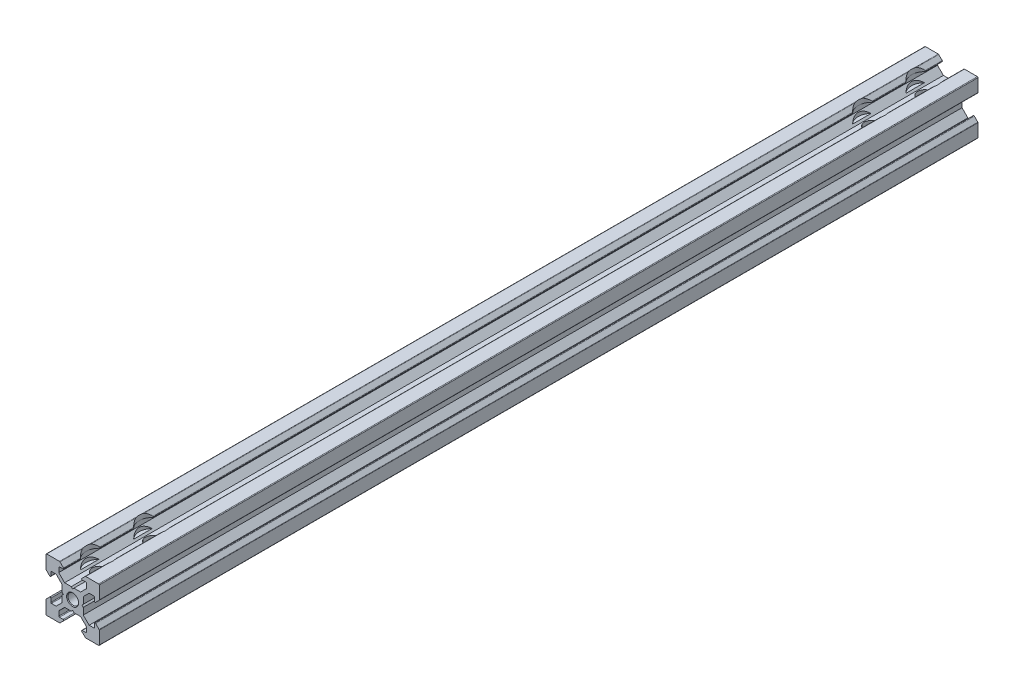
SolidWorks part; units mm, degrees
material "3.0205 (EN-AW 1200)"
ref_plane "Alzado" through (0, 0, 0) normal (0, 0, 1) x (1, 0, 0)
ref_plane "Planta" through (0, 0, 0) normal (0, 1, 0) x (1, 0, 0)
ref_plane "Vista lateral" through (0, 0, 0) normal (1, 0, 0) x (0, 0, -1)
sketch "Croquis1" plane through (0, 0, 0) normal (0, 0, 1) x (1, 0, 0)
  line L0 (-3.9878, 0.4994) -> (-3.4878, -0.0006)
  line L43 (0.0115, 3.5003) -> (-0.4882, 4)
  line L44 (-0.4882, 4) -> (-2.9967, 4)
  line L45 (-2.9967, 4) -> (-5.1969, 6.2003)
  line L46 (-5.1969, 6.2003) -> (-5.1969, 7.9432)
  line L47 (-4.9469, 8.1932) -> (-3.6023, 8.1932)
  line L53 (-7.9369, 5.2103) -> (-6.1869, 5.2103)
  line L54 (-6.1869, 5.2103) -> (-3.9878, 3.0113)
  line L55 (-3.9878, 3.0113) -> (-3.9878, 0.4994)
  line L58 (-8.1869, 4.9603) -> (-8.1869, 3.602)
  line L60 (-9.9869, 9.7494) -> (-9.9869, 4.902)
  line L61 (-9.7369, 9.9994) -> (-4.9084, 9.9994)
  line L62 (-8.6137, 3.4252) -> (-9.9137, 4.7252)
  line L64 (6.2124, 5.2094) -> (7.9554, 5.2094)
  line L65 (-3.4255, 8.62) -> (-4.7316, 9.9261)
  line L66 (4.0122, 3.0091) -> (6.2124, 5.2094)
  line L67 (4.0122, 0.5007) -> (4.0122, 3.0091)
  line L68 (3.5124, 0.001) -> (4.0122, 0.5007)
  line L71 (0.5115, 4.0003) -> (0.0115, 3.5003)
  line L72 (3.0234, 4.0003) -> (0.5115, 4.0003)
  line L73 (5.2225, 6.1994) -> (3.0234, 4.0003)
  line L74 (5.2225, 7.9494) -> (5.2225, 6.1994)
  line L75 (4.9725, 8.1994) -> (3.6141, 8.1994)
  line L76 (3.4374, 8.6261) -> (4.7374, 9.9261)
  line L77 (9.7615, 9.9994) -> (4.9141, 9.9994)
  line L78 (10.0115, 9.7494) -> (10.0115, 4.9208)
  line L79 (8.6322, 3.4379) -> (9.9383, 4.744)
  line L80 (8.2054, 4.9594) -> (8.2054, 3.6147)
  line L81 (5.2216, -6.2) -> (5.2216, -7.9429)
  line L82 (3.0213, -3.9997) -> (5.2216, -6.2)
  line L83 (0.5128, -3.9997) -> (3.0213, -3.9997)
  line L84 (0.0131, -3.5) -> (0.5128, -3.9997)
  line L87 (4.0124, -0.499) -> (3.5124, 0.001)
  line L88 (4.0124, -3.011) -> (4.0124, -0.499)
  line L89 (6.2115, -5.21) -> (4.0124, -3.011)
  line L90 (7.9615, -5.21) -> (6.2115, -5.21)
  line L91 (8.2115, -4.96) -> (8.2115, -3.6017)
  line L92 (8.6383, -3.4249) -> (9.9383, -4.7249)
  line L93 (10.0115, -9.749) -> (10.0115, -4.9017)
  line L94 (9.7615, -9.999) -> (4.933, -9.999)
  line L95 (3.4501, -8.6197) -> (4.7562, -9.9258)
  line L96 (4.9716, -8.1929) -> (3.6269, -8.1929)
  line L97 (-6.1878, -5.2091) -> (-7.9308, -5.2091)
  line L98 (-3.9876, -3.0088) -> (-6.1878, -5.2091)
  line L99 (-3.9876, -0.5004) -> (-3.9876, -3.0088)
  line L100 (-3.4878, -0.0006) -> (-3.9876, -0.5004)
  line L103 (-0.4869, -4) -> (0.0131, -3.5)
  line L104 (-2.9988, -4) -> (-0.4869, -4)
  line L105 (-5.1247, -6.1258) -> (-2.9988, -4)
  line L106 (-5.1979, -7.949) -> (-5.1979, -6.3026)
  line L107 (-4.9479, -8.199) -> (-3.5895, -8.199)
  line L108 (-3.4127, -8.6258) -> (-4.7127, -9.9258)
  line L109 (-9.7369, -9.999) -> (-4.8895, -9.999)
  line L110 (-9.9869, -9.749) -> (-9.9869, -4.9205)
  line L111 (-8.6076, -3.4376) -> (-9.9137, -4.7437)
  line L112 (-8.1808, -4.9591) -> (-8.1808, -3.6144)
  arc A0 (10.0115, -9.749) -> (9.7615, -9.999) centre (9.7615, -9.749) cw
  arc A1 (-9.7369, -9.999) -> (-9.9869, -9.749) centre (-9.7369, -9.749) cw
  arc A2 (10.0115, 9.7494) -> (9.7615, 9.9994) centre (9.7615, 9.7494) ccw
  arc A3 (-9.7369, 9.9994) -> (-9.9869, 9.7494) centre (-9.7369, 9.7494) ccw
  arc A4 (8.2115, -3.6017) -> (8.6383, -3.4249) centre (8.4615, -3.6017) cw
  arc A5 (7.9615, -5.21) -> (8.2115, -4.96) centre (7.9615, -4.96) ccw
  arc A6 (5.2216, -7.9429) -> (4.9716, -8.1929) centre (4.9716, -7.9429) cw
  arc A7 (3.4501, -8.6197) -> (3.6269, -8.1929) centre (3.6269, -8.4429) cw
  arc A8 (-3.5895, -8.199) -> (-3.4127, -8.6258) centre (-3.5895, -8.449) cw
  arc A9 (-5.1979, -7.949) -> (-4.9479, -8.199) centre (-4.9479, -7.949) ccw
  arc A10 (-5.1247, -6.1258) -> (-5.1979, -6.3026) centre (-4.9479, -6.3026) ccw
  arc A11 (-7.9308, -5.2091) -> (-8.1808, -4.9591) centre (-7.9308, -4.9591) cw
  arc A12 (-8.6076, -3.4376) -> (-8.1808, -3.6144) centre (-8.4308, -3.6144) cw
  arc A13 (8.6322, 3.4379) -> (8.2054, 3.6147) centre (8.4554, 3.6147) cw
  arc A14 (7.9554, 5.2094) -> (8.2054, 4.9594) centre (7.9554, 4.9594) cw
  arc A15 (5.2225, 7.9494) -> (4.9725, 8.1994) centre (4.9725, 7.9494) ccw
  arc A16 (3.6141, 8.1994) -> (3.4374, 8.6261) centre (3.6141, 8.4494) cw
  arc A17 (-3.6023, 8.1932) -> (-3.4255, 8.62) centre (-3.6023, 8.4432) ccw
  arc A18 (-8.6137, 3.4252) -> (-8.1869, 3.602) centre (-8.4369, 3.602) ccw
  arc A19 (-5.1969, 7.9432) -> (-4.9469, 8.1932) centre (-4.9469, 7.9432) cw
  arc A20 (-8.1869, 4.9603) -> (-7.9369, 5.2103) centre (-7.9369, 4.9603) cw
  arc A21 (9.9383, -4.7249) -> (10.0115, -4.9017) centre (9.7615, -4.9017) cw
  arc A22 (4.933, -9.999) -> (4.7562, -9.9258) centre (4.933, -9.749) cw
  arc A23 (10.0115, 4.9208) -> (9.9383, 4.744) centre (9.7615, 4.9208) cw
  arc A24 (4.7374, 9.9261) -> (4.9141, 9.9994) centre (4.9141, 9.7494) cw
  arc A25 (-4.7316, 9.9261) -> (-4.9084, 9.9994) centre (-4.9084, 9.7494) ccw
  arc A26 (-9.9137, 4.7252) -> (-9.9869, 4.902) centre (-9.7369, 4.902) cw
  arc A27 (-9.9869, -4.9205) -> (-9.9137, -4.7437) centre (-9.7369, -4.9205) cw
  arc A28 (-4.7127, -9.9258) -> (-4.8895, -9.999) centre (-4.8895, -9.749) cw
  dimension "D2" = 0.25
  dimension "D3" = 0.25
  dimension "D4" = 0.25
  dimension "D1" = 4
extrude "Saliente-Extruir1" add sketch "Croquis1" along normal blind 165 and the other way blind 165
sketch "Croquis4" plane through (0, 9.9994, 0) normal (0, 1, 0) x (1, 0, 0)
  line L0 (0.0115, 165) -> (0.0115, -165) construction
  point P0 (0.0115, -155)
  point P1 (0.0115, -135)
  point P4 (0.0115, 155)
  point P5 (0.0115, 135)
  dimension "D1" = 20
  dimension "D2" = 10
  dimension "D3" = 20
  dimension "D4" = 10
hole_wizard "Refrentado para tornillo con cabeza hueca de M51" positions "Croquis5" profile "Croquis6" counterbore size "M5" standard "ISO"
sketch "Croquis5" plane through (0, 9.9994, 0) normal (0, 1, 0) x (1, 0, 0)
  point P0 (0.0115, 155)
  point P3 (0.0115, 135)
  point P6 (0.0115, -135)
  point P9 (0.0115, -155)
sketch "Croquis6" plane through (0.0115, 9.9994, -155) normal (1, 0, 0) x (0, 0, 1)
  line L0 (0, 0) -> (0, 31.5923)
  line L1 (0, 31.5923) -> (2.65, 30)
  line L2 (2.65, 30) -> (2.65, 5.4)
  line L3 (2.65, 5.4) -> (5, 5.4)
  line L4 (5, 5.4) -> (5, 0)
  line L5 (5, 0) -> (0, 0)
  line L10 (0, 31.5923) -> (-2.65, 30) construction
  line L11 (0, -6.35) -> (0, 107.95) construction
  dimension "Diámetro de taladro" = 5.3
  dimension "Profundidad de taladro" = 30
  dimension "Diámetro de refrentado" = 10
  dimension "Profundidad de refrentado" = 5.4
  dimension "Ángulo de perforador" = 118
sketch "Croquis7" plane through (0, 0, 165) normal (0, 0, 1) x (1, 0, 0)
  circle A0 centre (0, 0) radius 2
  dimension "D1" = 4
extrude "Cortar-Extruir1" cut sketch "Croquis7" against normal through all
chamfer "Chaflán1" distance 0.25 angle 45 2 edges at (2, 0, -165) (2, 0, 165)
ref_plane "Plano2" through (0, 9.9994, 0) normal (0, 1, 0) x (1, 0, 0)
sketch "Croquis9" plane through (0, 9.9994, 0) normal (0, 1, 0) x (1, 0, 0)
  line L0 (0, 173.7191) -> (0, -224.7128) construction
